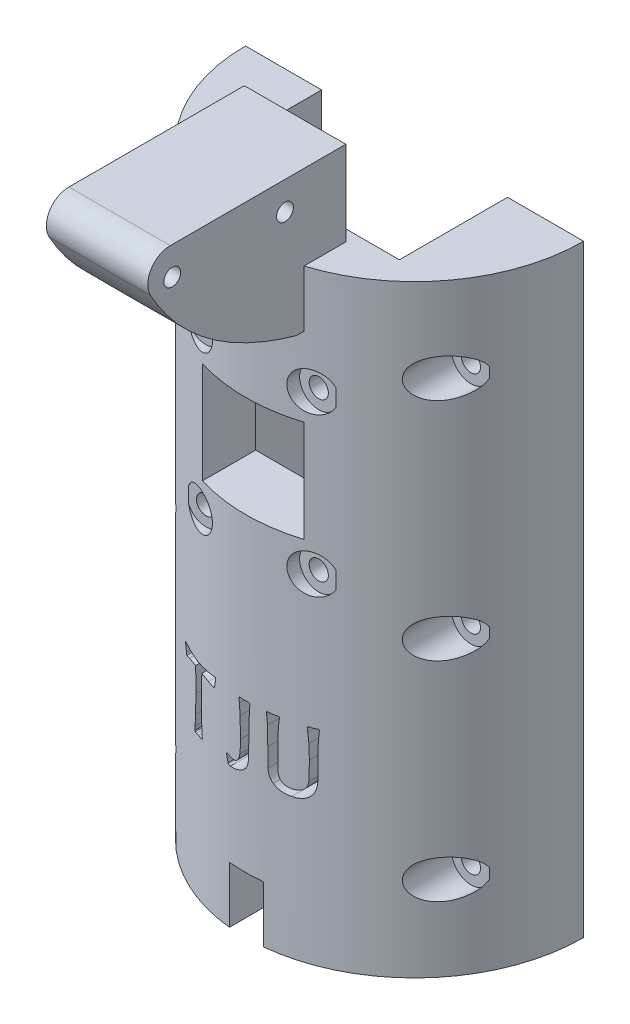
SolidWorks part; units mm, degrees
ref_plane "前视基准面" through (0, 0, 0) normal (0, 0, 1) x (1, 0, 0)
ref_plane "上视基准面" through (0, 0, 0) normal (0, 1, 0) x (1, 0, 0)
ref_plane "右视基准面" through (0, 0, 0) normal (1, 0, 0) x (0, 0, -1)
sketch "草图1" plane through (0, 0, 0) normal (0, 1, 0) x (1, 0, 0)
  line L0 (-30, 0) -> (30, 0)
  line L6 (15, 19.2) -> (-15, 19.2)
  line L7 (15, 19.2) -> (15, -19.2)
  line L8 (15, -19.2) -> (-15, -19.2)
  line L9 (-15, 19.2) -> (-15, -19.2)
  line L10 (15, 19.2) -> (-15, -19.2) construction
  line L11 (15, -19.2) -> (-15, 19.2) construction
  arc A0 (-30, 0) -> (30, 0) centre (0, 0) ccw
  point P0 (0, 0)
  dimension "D3" = 38.4
  dimension "D1" = 30
  dimension "D2" = 60
extrude "凸台-拉伸1" add sketch "草图1" along normal blind 80 contours L0 A0 L8 region at (-22.5, 0, 0.6708)
sketch "草图2" plane through (0, 0, 0) normal (0, 0, 1) x (1, 0, 0)
  line L0 (0, 122.0673) -> (0, -16.729) construction
  line L2 (-30, 0) -> (-15, 0) construction
  circle A0 centre (-10, 33) radius 1.7
  circle A1 centre (-10, 61) radius 1.7
  circle A2 centre (10, 33) radius 1.7
  circle A3 centre (10, 61) radius 1.7
  dimension "D1" = 20
  dimension "D2" = 20
  dimension "D3" = 33
  dimension "D4" = 28
extrude "切除-拉伸1" cut sketch "草图2" along normal blind 100
sketch "草图3" plane through (0, 0, 0) normal (0, 0, -1) x (-1, 0, 0)
  line L0 (-40.9161, 45) -> (57.667, 45) construction
  line L1 (-30, 80) -> (-30, 0) construction
  line L2 (30, 80) -> (30, 0) construction
  line L4 (-15, 80) -> (-30, 80) construction
  circle A0 centre (23.5, 65) radius 1.7
  circle A1 centre (-23.5, 65) radius 1.7
  circle A2 centre (23.5, 25) radius 1.7
  circle A3 centre (-23.5, 25) radius 1.7
  dimension "D1" = 40
  dimension "D2" = 40
  dimension "D3" = 6.5
  dimension "D4" = 6.5
  dimension "D5" = 15
extrude "切除-拉伸2" cut sketch "草图3" against normal blind 100
ref_plane "基准面1" through (0, 0, 40) normal (0, 0, -1) x (-1, 0, 0)
sketch "草图4" plane through (0, 0, 40) normal (0, 0, -1) x (-1, 0, 0)
  circle A0 centre (-23.5, 65) radius 3.4
  circle A1 centre (-23.5, 25) radius 3.4
  circle A2 centre (23.5, 65) radius 3.4
  circle A3 centre (23.5, 25) radius 3.4
extrude "切除-拉伸3" cut sketch "草图4" along normal blind 26.5
sketch "草图5" plane through (0, 0, 40) normal (0, 0, -1) x (-1, 0, 0)
  circle A0 centre (-10, 61) radius 3.4
  circle A1 centre (10, 61) radius 3.4
  circle A2 centre (-10, 33) radius 3.4
  circle A3 centre (10, 33) radius 3.4
extrude "切除-拉伸4" cut sketch "草图5" along normal blind 13 contours A2 | A3 | A1 | A0 region at (10, 61, 40) region at (-10, 61, 40) region at (10, 33, 40) region at (-10, 33, 40)
sketch "草图6" plane through (0, 0, 0) normal (0, -1, 0) x (1, 0, 0)
  line L0 (-30, 0) -> (30, 0)
  arc A0 (30, 0) -> (-30, 0) centre (0, 0) ccw
extrude "凸台-拉伸2" add sketch "草图6" along normal blind 3
sketch "草图7" plane through (0, -3, 0) normal (0, -1, 0) x (1, 0, 0)
  line L0 (-30, 0) -> (30, 0) construction
  line L1 (-6, 0) -> (6, 0)
  arc A0 (6, 0) -> (-6, 0) centre (0, 0) ccw
  dimension "D1" = 6
extrude "凸台-拉伸3" [suppressed] add sketch "草图7" along normal blind 9.5
sketch "草图8" plane through (0, 80, 0) normal (0, 1, 0) x (1, 0, 0)
  line L0 (0, 0) -> (0, -36.28) construction
  line L1 (-15, 0) -> (15, 0) construction
  line L2 (-7, -19.2) -> (7, -19.2)
  line L3 (15, -19.2) -> (-15, -19.2) construction
  line L4 (7, -19.2) -> (7, -29.1719)
  line L5 (-7, -19.2) -> (-7, -29.1719)
  arc A0 (-30, 0) -> (30, 0) centre (0, 0) ccw construction
  arc A1 (-7, -29.1719) -> (7, -29.1719) centre (0, 0) ccw
  point P8 (0, -19.2)
  dimension "D1" = 14
ref_plane "基准面2" through (0, 100, 0) normal (0, 1, 0) x (1, 0, 0)
sketch "草图9" plane through (0, 100, 0) normal (0, 1, 0) x (1, 0, 0)
  line L0 (0, 0) -> (0, -36.28) construction
  line L2 (-7, -19.2) -> (7, -19.2)
  line L3 (-7, -19.2) -> (-7, -64.2)
  line L4 (-7, -64.2) -> (7, -64.2)
  line L5 (7, -19.2) -> (7, -64.2)
  dimension "D1" = 14
  dimension "D2" = 45
ref_plane "基准面3" through (0, 70, 0) normal (0, 1, 0) x (1, 0, 0)
sketch "草图10" plane through (0, 70, 0) normal (0, 1, 0) x (1, 0, 0)
  line L0 (-15, 0) -> (15, 0) construction
  line L1 (-7, -29.1719) -> (-7, -19.2)
  line L2 (-7, -19.2) -> (7, -19.2)
  line L3 (7, -19.2) -> (7, -29.1719)
  arc A0 (-7, -29.1719) -> (7, -29.1719) centre (0, 0) ccw
sketch "草图13" plane through (0, 0, 0) normal (1, 0, 0) x (0, 0, -1)
  line L0 (-19.2, 100) -> (-60, 100)
  line L1 (-19.2, 100) -> (-64.2, 100) construction
  line L2 (-19.2, 100) -> (-64.2, 100) construction
  line L3 (-19.2, 100) -> (-19.2, 70)
  line L4 (-19.2, 70) -> (-29.1719, 70) construction
  line L5 (-29.1719, 70) -> (-19.2, 70) construction
  line L6 (-19.2, 70) -> (-30, 70)
  line L7 (-29.1719, 70) -> (-30, 70) construction
  line L8 (-30, 80) -> (-30, -3) construction
  line L9 (0, 80) -> (0, 0) construction
  spline S0 degree 2 poles (-60, 100) (-54.4581, 76.8596) (-30, 70) knots 0 0 0 1 1 1
  dimension "D1" = 19.2
extrude "凸台-拉伸4" add sketch "草图13" along normal mid plane 18
sketch "草图14" plane through (-9, 0, 0) normal (-1, 0, 0) x (0, 0, 1)
  line L0 (0, 80) -> (0, -3) construction
  line L1 (19.2, 100) -> (60, 100) construction
  circle A0 centre (32, 90) radius 1.5
  circle A1 centre (52, 90) radius 1.5
  dimension "D1" = 20
  dimension "D2" = 32
  dimension "D3" = 10
  dimension "D4" = 10
extrude "切除-拉伸6" cut sketch "草图14" against normal blind 18
sketch "草图17" plane through (0, 0, 0) normal (1, 0, 0) x (0, 0, -1)
  line L0 (0, 80) -> (0, -3) construction
  line L1 (-30, -3) -> (0, -3) construction
  circle A0 centre (0, 29) radius 3
  circle A1 centre (0, 49) radius 3
  dimension "D1" = 6
  dimension "D2" = 32
  dimension "D3" = 2
sketch "草图18" plane through (0, 100, 0) normal (0, 1, 0) x (1, 0, 0)
  line L0 (9, -19.2) -> (9, -60) construction
  line L1 (-9, -19.2) -> (9, -19.2)
  line L2 (-9, -19.2) -> (-9, -21.2)
  line L3 (-9, -21.2) -> (9, -21.2)
  line L4 (9, -19.2) -> (9, -21.2)
  dimension "D1" = 2
extrude "切除-拉伸9" cut sketch "草图18" against normal blind 20
sketch "草图19" plane through (0, 0, 0) normal (0, 1, 0) x (1, 0, 0)
  circle A0 centre (0, 0) radius 3
extrude "切除-拉伸10" [suppressed] cut sketch "草图19" against normal blind 3
ref_plane "基准面4" through (0, 16, 0) normal (0, 1, 0) x (1, 0, 0)
fillet "圆角4" [suppressed] radius 1
chamfer "倒角2" [suppressed] distance 2 angle 45
sketch "草图20" plane through (0, -3, 0) normal (0, -1, 0) x (1, 0, 0)
  line L0 (-30, 0) -> (30, 0) construction
  circle A0 centre (0, 20.5) radius 6
  dimension "D1" = 12
  dimension "D2" = 20.5
extrude "切除-拉伸11" [suppressed] cut sketch "草图20" against normal blind 15
sketch "草图23" [suppressed] plane through (0, 0, 19.2) normal (0, 0, -1) x (-1, 0, 0)
  line L1 (-5.8575, 12) -> (2.8125, 12)
  line L2 (-5.8575, 12) -> (-5.8575, -3.4639)
  line L3 (-5.8575, -3.4639) -> (2.8125, -3.4639)
  line L4 (2.8125, 12) -> (2.8125, -3.4639)
extrude "切除-拉伸14" [suppressed] cut sketch "草图23" against normal blind 30
sketch "草图25" plane through (0, 100, 0) normal (0, 1, 0) x (1, 0, 0)
  line L1 (-9, -21.2) -> (9, -21.2)
  line L2 (-9, -21.2) -> (-9, -60)
  line L3 (-9, -60) -> (9, -60)
  line L4 (9, -21.2) -> (9, -60)
extrude "切除-拉伸16" cut sketch "草图25" against normal blind 5
fillet "圆角6" radius 4 1 edges at (0, 95, 58.5139)
sketch "草图28" plane through (0, -3, 0) normal (0, -1, 0) x (1, 0, 0)
  line L5 (-30, 0) -> (30, 0)
  line L8 (-30, 0) -> (30, 0)
  arc A4 (30, 0) -> (-30, 0) centre (0, 0) ccw
  arc A7 (30, 0) -> (-30, 0) centre (0, 0) ccw
  dimension "D1" = 0
extrude "凸台-拉伸7" add sketch "草图28" along normal blind 19
sketch "草图26" [suppressed] plane through (0, -3, 0) normal (0, -1, 0) x (1, 0, 0)
  line L0 (-2.8125, 25.8) -> (-2.8125, 29.8679)
  line L1 (5.8575, 29.4226) -> (5.8575, 21.8)
  line L2 (-30, 0) -> (30, 0)
  arc A2 (-2.8125, 25.8) -> (5.8575, 21.8) centre (0, 20.5) ccw
  arc A3 (6, 0) -> (-6, 0) centre (0, 0) ccw
  arc A4 (30, 0) -> (-30, 0) centre (0, 0) ccw
extrude "凸台-拉伸5" [suppressed] add sketch "草图26" along normal blind 2
sketch "草图27" [suppressed] plane through (0, -12.5, 0) normal (0, -1, 0) x (1, 0, 0)
  line L0 (-6, 0) -> (6, 0)
  arc A0 (6, 0) -> (-6, 0) centre (0, 0) ccw
extrude "凸台-拉伸6" [suppressed] add sketch "草图27" along normal blind 2
sketch "草图29" plane through (0, 0, 0) normal (0, 1, 0) x (1, 0, 0)
  line L1 (15, -19.2) -> (-15, -19.2)
  line L2 (15, -19.2) -> (15, 0)
  line L3 (15, 0) -> (-15, 0)
  line L4 (-15, -19.2) -> (-15, 0)
extrude "切除-拉伸17" cut sketch "草图29" against normal up to next
sketch "草图30" plane through (0, -22, 0) normal (0, -1, 0) x (1, 0, 0)
  line L0 (30, 0) -> (-30, 0)
  line L5 (15, 19.2) -> (15, 0)
  line L6 (15, 0) -> (30, 0)
  line L7 (-30, 0) -> (-15, 0)
  line L8 (-15, 0) -> (-15, 19.2)
  line L9 (-15, 19.2) -> (15, 19.2)
  arc A1 (30, 0) -> (-30, 0) centre (0, 0) ccw
  arc A2 (30, 0) -> (-30, 0) centre (0, 0) ccw
  dimension "D1" = 0
extrude "凸台-拉伸9" add sketch "草图30" along normal blind 5
sketch "草图31" plane through (0, -22, 0) normal (0, 1, 0) x (1, 0, 0)
  line L0 (-15, 0) -> (15, 0) construction
  circle A0 centre (0, 0) radius 3
  dimension "D1" = 6
extrude "切除-拉伸18" cut sketch "草图31" against normal blind 3
fillet "圆角7" radius 1 1 edges at (0, -25, 3)
chamfer "倒角3" distance 2 angle 45 1 edges at (0, -22, 3)
sketch "草图32" plane through (15, 0, 0) normal (-1, 0, 0) x (0, 0, 1)
  line L4 (0, 80) -> (0, -22)
  line L5 (0, -22) -> (19.2, -22)
  line L6 (19.2, -22) -> (19.2, 80)
  line L7 (19.2, 80) -> (0, 80)
  line L8 (0, 80) -> (0, -22)
  line L9 (0, -22) -> (19.2, -22)
  line L10 (19.2, -22) -> (19.2, 80)
  line L11 (19.2, 80) -> (0, 80)
  dimension "D1" = 0
extrude "切除-拉伸19" cut sketch "草图32" against normal blind 1.5
sketch "草图33" plane through (-15, 0, 0) normal (1, 0, 0) x (0, 0, -1)
  line L4 (-19.2, 80) -> (-19.2, -22)
  line L5 (-19.2, -22) -> (0, -22)
  line L6 (0, -22) -> (0, 80)
  line L7 (0, 80) -> (-19.2, 80)
  line L8 (-19.2, 80) -> (-19.2, -22)
  line L9 (-19.2, -22) -> (0, -22)
  line L10 (0, -22) -> (0, 80)
  line L11 (0, 80) -> (-19.2, 80)
  dimension "D1" = 0
extrude "切除-拉伸20" cut sketch "草图33" against normal blind 1.5
sketch "草图34" plane through (0, -27, 0) normal (0, -1, 0) x (1, 0, 0)
  line L0 (-6, 0) -> (6, 0)
  arc A0 (6, 0) -> (-6, 0) centre (0, 0) ccw
  dimension "D1" = 6
extrude "凸台-拉伸10" add sketch "草图34" along normal blind 9.5
sketch "草图35" plane through (0, -27, 0) normal (0, -1, 0) x (1, 0, 0)
  line L0 (-6, 0) -> (6, 0) construction
  circle A0 centre (0, 18.5) radius 5
  dimension "D1" = 10
  dimension "D2" = 18.5
extrude "切除-拉伸21" cut sketch "草图35" against normal blind 15
sketch "草图36" plane through (0, 0, 19.2) normal (0, 0, -1) x (-1, 0, 0)
  line L2 (-3, -27) -> (3, -27)
  line L4 (-3, -27) -> (-3, -17)
  line L5 (-3, -17) -> (3, -17)
  line L6 (3, -27) -> (3, -17)
  line L7 (0, -17) -> (0, -27) construction
  line L8 (-3, -27) -> (3, -27) construction
  point P2 (0, -27)
  dimension "D1" = 6
extrude "切除-拉伸22" cut sketch "草图36" against normal blind 15
sketch "草图39" plane through (0, 0, 0) normal (0, 0, -1) x (-1, 0, 0)
  line L0 (-30, 80) -> (-30, -27) construction
  line L4 (-6, -27) -> (-30, -27) construction
  line L5 (30, 80) -> (30, -27) construction
  line L6 (30, -27) -> (6, -27) construction
  circle A0 centre (-23.5, -12) radius 1.7
  circle A2 centre (23.5, -12) radius 1.7
  dimension "D3" = 3.4
  dimension "D5" = 3.4
  dimension "D1" = 6.5
  dimension "D2" = 15
  dimension "D4" = 6.5
  dimension "D6" = 15
extrude "切除-拉伸23" cut sketch "草图39" against normal through all
sketch "草图40" plane through (0, 0, 40) normal (0, 0, -1) x (-1, 0, 0)
  circle A0 centre (-23.5, -12) radius 3.4
  circle A1 centre (23.5, -12) radius 3.4
  dimension "D1" = 6.8
  dimension "D2" = 6.8
extrude "切除-拉伸25" cut sketch "草图40" along normal blind 26.5
sketch "草图41" plane through (0, 0, 40) normal (0, 0, -1) x (-1, 0, 0)
  line L0 (0, 0) -> (0, 67.5936) construction
  line L1 (-9, 80) -> (-30, 80) construction
  line L2 (9, 56) -> (-9, 56)
  line L3 (9, 56) -> (9, 38)
  line L4 (9, 38) -> (-9, 38)
  line L5 (-9, 56) -> (-9, 38)
  line L6 (0, 38) -> (0, 56) construction
  line L7 (9, 47) -> (-9, 47) construction
  point P3 (0, 47)
  dimension "D1" = 33
  dimension "D2" = 18
  dimension "D3" = 18
extrude "切除-拉伸26" cut sketch "草图41" along normal through all
sketch "草图43" plane through (0, 0, 40) normal (0, 0, -1) x (-1, 0, 0)
  text T0 "TJU" font "华康龙门石碑W9" height in points 44
extrude "切除-拉伸27" cut sketch "草图43" along normal through all
sketch "草图46" plane through (0, -36.5, 0) normal (0, -1, 0) x (1, 0, 0)
  line L0 (0, -6) -> (0, 10.9547) construction
  line L1 (-1.95, 7.9743) -> (1.95, 7.9743)
  line L2 (1.95, 7.9743) -> (1.95, 5.6743)
  line L3 (-1.95, 7.9743) -> (-1.95, 5.6743)
  arc A0 (1.95, 5.6743) -> (-1.95, 5.6743) centre (0, 0) ccw
  point P9 (0, 7.9743)
  dimension "D2" = 12
  dimension "D1" = 1.95
  dimension "D3" = 2.3
extrude "凸台-拉伸11" add sketch "草图46" against normal up to next
